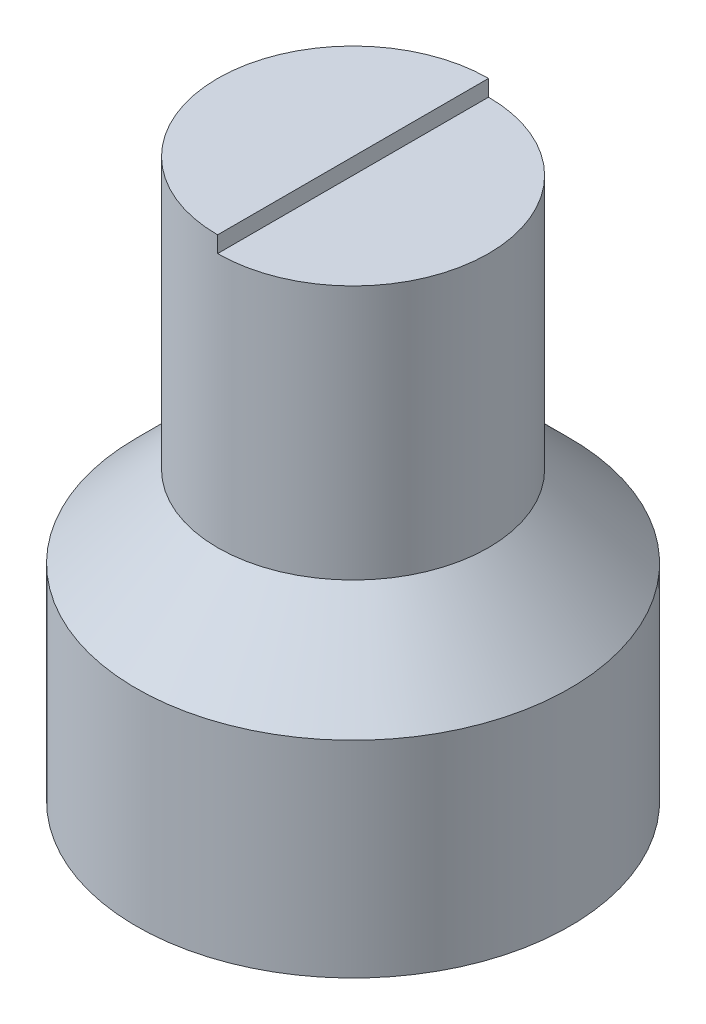
SolidWorks part; units mm, degrees
material "Простая углеродистая сталь"
ref_plane "Front" through (0, 0, 0) normal (0, 0, 1) x (1, 0, 0)
ref_plane "Top" through (0, 0, 0) normal (0, 1, 0) x (1, 0, 0)
ref_plane "Right" through (0, 0, 0) normal (1, 0, 0) x (0, 0, -1)
sketch "Эскиз1" plane through (0, 0, 0) normal (0, 0, 1) x (1, 0, 0)
  line L1 (0, 10.3) -> (-5, 10.3)
  line L9 (0, -10.3) -> (-8, -10.3)
  line L10 (0, 10.3) -> (0, -10.3)
  line L11 (-8, -10.3) -> (-8, 0.3)
  line L12 (-8, 0.3) -> (-5, 0.3)
  line L13 (-5, 0.3) -> (-5, 10.3)
  point P0 (0, 0)
  dimension "D1" = 10
  dimension "D2" = 8
  dimension "D5" = 5
  dimension "D6" = 20.6
revolve "База" add sketch "Эскиз1" angle 360 about L10
sketch "Эскиз4" plane through (0, 10.3, 0) normal (0, 1, 0) x (1, 0, 0)
  line L0 (0, 0) -> (5, -5) construction
  line L8 (0, -5) -> (5, -5)
  line L9 (5, 5) -> (5, -5)
  line L10 (0, -5) -> (0, 5)
  line L11 (0, 5) -> (5, 5)
  circle A1 centre (0, 0) radius 5 construction
  circle A2 centre (0, 0) radius 5 construction
  point P0 (0, 0)
  dimension "D1" = 45
extrude "Основание платы" cut sketch "Эскиз4" against normal blind 0.6
chamfer "Фаска1" distance 3 angle 45 1 edges at (-8, 0.3, 0)
sketch "Эскиз5" plane through (0, -10.3, 0) normal (0, -1, 0) x (1, 0, 0)
  circle A0 centre (0, 0) radius 5.1
  dimension "D1" = 10.2
extrude "Магнит" cut sketch "Эскиз5" against normal blind 5.1
hole_wizard "Крепление магнита M3" positions "Эскиз2" profile "Эскиз3" tap size "M3" standard "ISO"
sketch "Эскиз2" plane through (0, -5.2, 0) normal (0, -1, 0) x (-1, 0, 0)
  point P0 (0, 0)
cosmetic thread "Отверстие резьбы1" parameters "D1"=8, "D2"=3
sketch "Эскиз3" plane through (0, -5.2, 0) normal (1, 0, 0) x (0, 0, -1)
  line L0 (0, 0) -> (0, 10.7511)
  line L1 (0, 10.7511) -> (1.25, 10)
  line L2 (1.25, 10) -> (1.25, 0)
  line L5 (1.25, 0) -> (0, 0)
  line L10 (0, 10.7511) -> (-1.25, 10) construction
  line L11 (0, -6.35) -> (0, 107.95) construction
  dimension "Диаметр сверла" = 2.5
  dimension "Глубина сверла" = 10
  dimension "Угол заточки сверла" = 118
